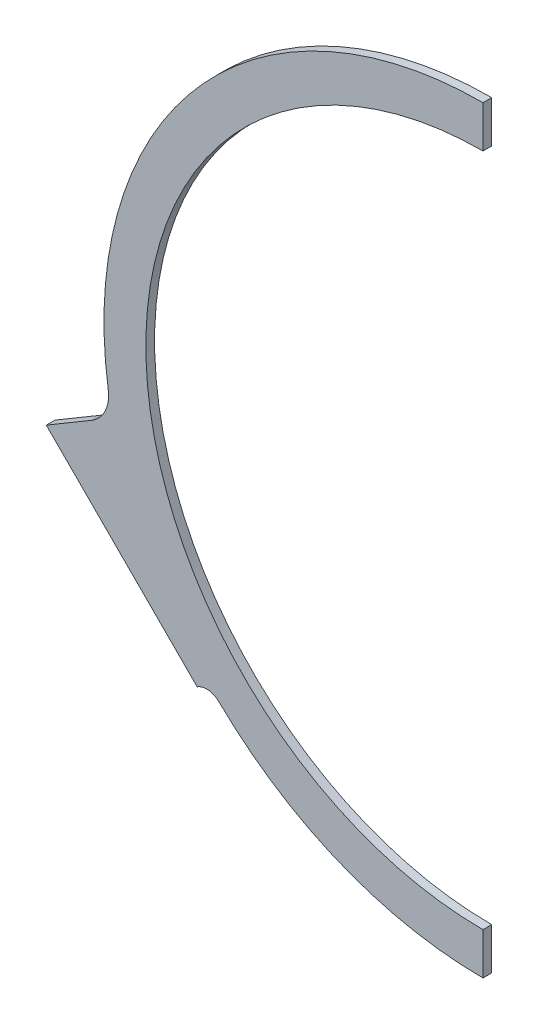
SolidWorks part; units mm, degrees
material "Balsa"
ref_plane "Front Plane" through (0, 0, 0) normal (0, 0, 1) x (1, 0, 0)
ref_plane "Top Plane" through (0, 0, 0) normal (0, 1, 0) x (1, 0, 0)
ref_plane "Right Plane" through (0, 0, 0) normal (1, 0, 0) x (0, 0, -1)
sketch "Sketch1" plane through (0, 0, 0) normal (0, 0, 1) x (1, 0, 0)
  line L0 (0, 0) -> (0, 499.9473) construction
  line L1 (0, -114.7984) -> (0, -129.4545) construction
  line L2 (0, -374.4718) -> (0, 404.2655) construction
  line L3 (-1.651, 142.9921) -> (-1.651, 150.6121) construction
  line L4 (1.651, 142.9921) -> (1.651, 150.6121) construction
  line L5 (-1.651, 142.9921) -> (1.651, 142.9921) construction
  line L6 (136.2041, -53.806) -> (0.0002, 24.7625) construction
  line L7 (-136.2076, -53.7991) -> (0.0002, 24.7625) construction
  line L8 (136.2041, -53.806) -> (0.0002, 24.7625) construction
  line L9 (-136.2076, -53.7991) -> (0.0002, 24.7625) construction
  line L10 (-125.0584, -45.4626) -> (-118.4576, -41.6554) construction
  line L11 (-123.6259, -48.4483) -> (-116.8078, -44.5157) construction
  line L12 (-118.4576, -41.6554) -> (-116.8078, -44.5157) construction
  line L13 (-124.1455, -48.7479) -> (-123.6847, -48.4822) construction
  line L14 (-123.6847, -48.4822) -> (-123.6259, -48.4483) construction
  line L15 (-125.7952, -45.8876) -> (-125.1113, -45.4931) construction
  line L16 (-125.1113, -45.4931) -> (-125.0584, -45.4626) construction
  line L17 (125.4797, -45.7137) -> (125.1075, -45.499) construction
  line L18 (123.8298, -48.5739) -> (123.6807, -48.488) construction
  line L19 (117.0223, -44.647) -> (118.6722, -41.7868) construction
  line L20 (123.6807, -48.488) -> (123.6228, -48.4545) construction
  line L21 (123.6228, -48.4545) -> (117.0223, -44.647) construction
  line L22 (125.1075, -45.499) -> (125.0554, -45.4689) construction
  line L23 (125.0554, -45.4689) -> (118.6722, -41.7868) construction
  line L24 (-107.079, -46.8884) -> (-120.3798, -54.5735)
  line L25 (-108.6638, -44.1348) -> (-121.9647, -51.8199)
  line L28 (-115.4206, -47.9666) -> (-121.9445, -51.7361) construction
  line L29 (-120.2754, -54.5131) -> (-108.646, -44.1245) construction
  line L30 (-114.4607, -49.3188) -> (-122.1124, -53.7399) construction
  line L31 (-113.7686, -50.8257) -> (-120.3665, -54.6379) construction
  line L32 (-115.4206, -47.9666) -> (-113.7686, -50.8257) construction
  line L33 (106.3137, -46.4532) -> (129.9098, -60.0883)
  line L34 (107.9004, -43.7007) -> (131.505, -57.3407)
  line L35 (129.9098, -60.0883) -> (131.505, -57.3407)
  line L36 (129.9098, -60.0883) -> (131.505, -57.3407) construction
  line L37 (107.9004, -43.7007) -> (131.505, -57.3407) construction
  line L38 (106.3137, -46.4532) -> (129.9098, -60.0883) construction
  line L39 (129.9098, -60.0883) -> (107.9004, -43.7007) construction
  line L40 (118.9051, -51.8945) -> (101.8722, -42.0519) construction
  line L41 (120.3631, -54.6438) -> (113.7655, -50.8313)
  line L42 (122.0152, -51.7848) -> (122.0057, -51.7794) construction
  line L43 (113.7655, -50.8313) -> (115.4176, -47.9723)
  line L44 (122.0057, -51.7794) -> (121.9413, -51.7421) construction
  line L45 (121.9413, -51.7421) -> (115.4176, -47.9723)
  line L46 (-108.6638, -44.1348) -> (-121.9647, -51.8199)
  line L47 (-107.079, -46.8884) -> (-120.3798, -54.5735)
  arc A0 (-1.651, 150.6121) -> (-125.0584, -45.4626) centre (0, 12.7) ccw
  circle A1 centre (0, 12.7) radius 120.904
  arc A2 (0, 150.622) -> (-1.651, 150.6121) centre (0, 12.7) ccw
  circle A3 centre (0, 12.7) radius 137.922 construction
  arc A4 (1.651, 150.6121) -> (0, 150.622) centre (0, 12.7) ccw
  arc A5 (-124.3508, -46.9604) -> (-123.6259, -48.4483) centre (0, 12.7) ccw
  arc A6 (-123.6259, -48.4483) -> (-121.9445, -51.7361) centre (0, 12.7) ccw
  arc A7 (-125.0584, -45.4626) -> (-124.3508, -46.9604) centre (0, 12.7) ccw
  arc A8 (124.3477, -46.9667) -> (125.0554, -45.4689) centre (0, 12.7) ccw
  arc A9 (125.0554, -45.4689) -> (1.651, 150.6121) centre (0, 12.7) ccw
  arc A10 (123.6228, -48.4545) -> (124.3477, -46.9667) centre (0, 12.7) ccw
  arc A11 (-121.9153, -51.7914) -> (-121.1641, -53.1919) centre (0, 12.7) ccw
  arc A12 (-120.3665, -54.6379) -> (120.3631, -54.6438) centre (0, 12.7) ccw
  arc A13 (-121.9445, -51.7361) -> (-121.9153, -51.7914) centre (0, 12.7) ccw
  arc A14 (-121.1641, -53.1919) -> (-120.3827, -54.6089) centre (0, 12.7) ccw
  arc A15 (-120.3827, -54.6089) -> (-120.397, -54.5834) centre (0, 12.7) ccw construction
  arc A16 (-120.397, -54.5834) -> (-120.3665, -54.6379) centre (0, 12.7) ccw construction
  arc A17 (120.3936, -54.5893) -> (121.0149, -53.4654) centre (0, 12.7) ccw construction
  arc A18 (121.9413, -51.7421) -> (123.6228, -48.4545) centre (0, 12.7) ccw
  arc A19 (120.3631, -54.6438) -> (120.3936, -54.5893) centre (0, 12.7) ccw construction
  arc A20 (121.0149, -53.4654) -> (121.9121, -51.7974) centre (0, 12.7) ccw construction
  arc A21 (121.9121, -51.7974) -> (121.9413, -51.7421) centre (0, 12.7) ccw construction
  spline S0 degree 3 poles (106.3137, -46.4532) (106.8426, -45.5357) (107.3715, -44.6182) (107.9004, -43.7007) knots 0 0 0 0 1 1 1 1 weights 1 1 1 1
  spline S1 degree 3 poles (-66.0123, 133.6164) (-70.0128, 131.4329) (-73.8716, 129.0699) (-81.3156, 123.9975) (-84.9009, 121.288) (-91.7995, 115.5249) (-95.113, 112.4712) (-99.0811, 108.4341) (-99.866, 107.6157) (-101.4182, 105.9565) (-102.1865, 105.1147) (-104.4569, 102.5643) (-105.9223, 100.8334) (-110.1768, 95.5512) (-115.4725, 88.2691) (-120.0285, 80.5179) (-123.1654, 74.5269) (-124.1643, 72.5002) (-125.5914, 69.415) (-126.0551, 68.3791) (-126.9587, 66.292) (-127.3989, 65.2397) (-129.5278, 59.9684) (-131.0098, 55.7) (-133.5456, 47.0638) (-134.5993, 42.696) (-136.2795, 33.8613) (-136.906, 29.3944) (-137.415, 23.7472) (-137.5031, 22.6146) (-137.6514, 20.3429) (-137.7116, 19.2049) (-137.8496, 15.7999) (-137.8852, 13.5361) (-137.8263, 6.7629) (-137.3062, -2.2197) (-135.9163, -11.1068) (-134.5433, -17.7359) (-134.0304, -19.9395) (-132.8922, -24.3345) (-132.2653, -26.5303) (-130.2347, -33.03) (-128.6774, -37.2656) (-126.1245, -43.2881) (-125.286, -45.1501) (-124.4066, -46.9926) knots 0 0 0 0 0.03125 0.03125 0.0625 0.0625 0.09375 0.09375 0.101563 0.101563 0.109375 0.109375 0.125 0.125 0.15625 0.1875 0.1875 0.203125 0.203125 0.210938 0.210938 0.21875 0.21875 0.25 0.25 0.28125 0.28125 0.3125 0.3125 0.320313 0.320313 0.328125 0.328125 0.34375 0.34375 0.375 0.40625 0.40625 0.421875 0.421875 0.4375 0.4375 0.46875 0.46875 0.48295 0.48295 0.48295 0.48295 construction
  spline S2 degree 3 poles (-2953.7904, 2461.9899) (-820.777, 189.8449) (-138.9507, -249.535) (81.4542, -98.9353) (85.033, -96.2237) (91.9188, -90.4573) (95.2258, -87.4025) (99.1858, -83.3647) (99.9691, -82.5461) (101.5182, -80.8868) (102.2849, -80.0449) (104.5506, -77.4941) (106.013, -75.7632) (110.2586, -70.4809) (112.9006, -66.8403) (117.8152, -59.3254) (120.0877, -55.4512) (123.2166, -49.4629) (124.2129, -47.4373) (125.6361, -44.3538) (126.0986, -43.3185) (126.9997, -41.2327) (127.4386, -40.181) (129.5618, -34.9121) (131.0396, -30.646) (133.5674, -22.0152) (134.6173, -17.6505) (136.2906, -8.8227) (136.914, -4.3596) (137.4197, 1.2823) (137.5071, 2.4139) (137.6542, 4.6834) (137.7138, 5.8206) (137.85, 9.2232) (137.8846, 11.4853) (137.8228, 18.2533) (137.2995, 27.2283) (135.9081, 36.1069) (134.5347, 42.7292) (134.0218, 44.9305) (132.8839, 49.3207) (132.2571, 51.5145) (130.2267, 58.0093) (128.67, 62.2416) (125.1615, 70.5162) (123.2097, 74.5586) (118.9108, 82.4534) (116.5637, 86.3058) (113.3753, 90.999) (112.7241, 91.9325) (111.3996, 93.7822) (110.7272, 94.697) (108.6802, 97.4113) (107.2757, 99.181) (102.9447, 104.3725) (96.8571, 110.9816) (90.1513, 116.9722) (84.8861, 121.2292) (83.0917, 122.6088) (80.3399, 124.6181) (79.4113, 125.2786) (77.543, 126.5731) (76.6028, 127.2075) (71.8708, 130.3161) (67.9881, 132.6004) (60.0328, 136.7739) (55.9603, 138.6631) (47.6249, 142.0446) (43.3619, 143.537) (37.9102, 145.1462) (36.8136, 145.4551) (34.6205, 146.0438) (33.5224, 146.3241) (30.2234, 147.1229) (28.0179, 147.5997) (21.3832, 148.8649) (16.9358, 149.4889) (7.993, 150.3014) (3.4975, 150.4899) (-3.2824, 150.4396) (-5.5486, 150.3672) (-10.0934, 150.1088) (-12.3559, 149.9236) (-19.101, 149.2046) (-23.5473, 148.5072) (-32.3412, 146.6856) (-36.6887, 145.5614) (-43.1354, 143.5526) (-45.2718, 142.8291) (-49.5193, 141.273) (-51.6323, 140.4395) (-369.2659, 5.9249) (-132.0865, -1278.1783) (677.8124, -3754.3927) knots -1.791229 -1.791229 -1.791229 -1.791229 0.03125 0.03125 0.0625 0.0625 0.09375 0.09375 0.101563 0.101563 0.109375 0.109375 0.125 0.125 0.15625 0.15625 0.1875 0.1875 0.203125 0.203125 0.210938 0.210938 0.21875 0.21875 0.25 0.25 0.28125 0.28125 0.3125 0.3125 0.320313 0.320313 0.328125 0.328125 0.34375 0.34375 0.375 0.40625 0.40625 0.421875 0.421875 0.4375 0.4375 0.46875 0.46875 0.5 0.5 0.53125 0.53125 0.539062 0.539062 0.546875 0.546875 0.5625 0.5625 0.59375 0.625 0.625 0.640625 0.640625 0.648437 0.648437 0.65625 0.65625 0.6875 0.6875 0.71875 0.71875 0.75 0.75 0.757812 0.757812 0.765625 0.765625 0.78125 0.78125 0.8125 0.8125 0.84375 0.84375 0.859375 0.859375 0.875 0.875 0.90625 0.90625 0.9375 0.9375 0.953125 0.953125 0.96875 0.96875 3.320852 3.320852 3.320852 3.320852 only from (66.1767, -108.566) to (-66.0123, 133.6164)
  spline S3 degree 3 poles (66.1767, -108.566) (70.1708, -106.3789) (74.0231, -104.0129) (81.4542, -98.9353) (85.033, -96.2237) (91.9188, -90.4573) (95.2258, -87.4025) (99.1858, -83.3647) (99.9691, -82.5461) (101.5182, -80.8868) (102.2849, -80.0449) (104.5506, -77.4941) (106.013, -75.7632) (110.2586, -70.4809) (112.9006, -66.8403) (117.8152, -59.3254) (120.0877, -55.4512) (123.2166, -49.4629) (124.2129, -47.4373) (125.6361, -44.3538) (126.0986, -43.3185) (126.9997, -41.2327) (127.4386, -40.181) (129.5618, -34.9121) (131.0396, -30.646) (133.5674, -22.0152) (134.6173, -17.6505) (136.2906, -8.8227) (136.914, -4.3596) (137.4197, 1.2823) (137.5071, 2.4139) (137.6542, 4.6834) (137.7138, 5.8206) (137.85, 9.2232) (137.8846, 11.4853) (137.8228, 18.2533) (137.2995, 27.2283) (135.9081, 36.1069) (134.5347, 42.7292) (134.0218, 44.9305) (132.8839, 49.3207) (132.2571, 51.5145) (130.2267, 58.0093) (128.67, 62.2416) (125.1615, 70.5162) (123.2097, 74.5586) (118.9108, 82.4534) (116.5637, 86.3058) (113.3753, 90.999) (112.7241, 91.9325) (111.3996, 93.7822) (110.7272, 94.697) (108.6802, 97.4113) (107.2757, 99.181) (102.9447, 104.3725) (96.8571, 110.9816) (90.1513, 116.9722) (84.8861, 121.2292) (83.0917, 122.6088) (80.3399, 124.6181) (79.4113, 125.2786) (77.543, 126.5731) (76.6028, 127.2075) (71.8708, 130.3161) (67.9881, 132.6004) (60.0328, 136.7739) (55.9603, 138.6631) (47.6249, 142.0446) (43.3619, 143.537) (37.9102, 145.1462) (36.8136, 145.4551) (34.6205, 146.0438) (33.5224, 146.3241) (30.2234, 147.1229) (28.0179, 147.5997) (21.3832, 148.8649) (16.9358, 149.4889) (7.993, 150.3014) (3.4975, 150.4899) (-3.2824, 150.4396) (-5.5486, 150.3672) (-10.0934, 150.1088) (-12.3559, 149.9236) (-19.101, 149.2046) (-23.5473, 148.5072) (-32.3412, 146.6856) (-36.6887, 145.5614) (-43.1354, 143.5526) (-45.2718, 142.8291) (-49.5193, 141.273) (-51.6323, 140.4395) (-57.9206, 137.7764) (-62.0153, 135.798) (-66.0123, 133.6164) knots 0 0 0 0 0.03125 0.03125 0.0625 0.0625 0.09375 0.09375 0.101563 0.101563 0.109375 0.109375 0.125 0.125 0.15625 0.15625 0.1875 0.1875 0.203125 0.203125 0.210938 0.210938 0.21875 0.21875 0.25 0.25 0.28125 0.28125 0.3125 0.3125 0.320313 0.320313 0.328125 0.328125 0.34375 0.34375 0.375 0.40625 0.40625 0.421875 0.421875 0.4375 0.4375 0.46875 0.46875 0.5 0.5 0.53125 0.53125 0.539062 0.539062 0.546875 0.546875 0.5625 0.5625 0.59375 0.625 0.625 0.640625 0.640625 0.648437 0.648437 0.65625 0.65625 0.6875 0.6875 0.71875 0.71875 0.75 0.75 0.757812 0.757812 0.765625 0.765625 0.78125 0.78125 0.8125 0.8125 0.84375 0.84375 0.859375 0.859375 0.875 0.875 0.90625 0.90625 0.9375 0.9375 0.953125 0.953125 0.96875 0.96875 1 1 1 1 construction
  spline S4 degree 3 poles (-124.4066, -46.9926) (-124.169, -47.4906) (-123.9283, -47.9871) (-123.6847, -48.4822) knots 0.48295 0.48295 0.48295 0.48295 0.486788 0.486788 0.486788 0.486788 construction
  spline S5 degree 3 poles (-123.6847, -48.4822) (-122.846, -50.1865) (-121.9718, -51.874) (-118.9108, -57.4955) (-116.5612, -61.3517) (-113.369, -66.0497) (-112.7169, -66.9844) (-111.3913, -68.8351) (-110.7184, -69.7503) (-108.6697, -72.4662) (-107.264, -74.2369) (-102.929, -79.4315) (-96.8353, -86.0447) (-90.1214, -92.0392) (-84.8493, -96.299) (-83.0524, -97.6795) (-80.2967, -99.6899) (-79.367, -100.3507) (-77.4971, -101.6451) (-76.5559, -102.2795) (-71.8198, -105.3881) (-67.9332, -107.6723) (-59.9695, -111.8452) (-55.8924, -113.7339) (-47.5468, -117.114) (-43.2782, -118.6053) (-37.8188, -120.2127) (-36.7216, -120.521) (-34.5268, -121.1085) (-33.4279, -121.3881) (-30.1264, -122.185) (-27.9191, -122.6605) (-21.2788, -123.9216) (-16.8274, -124.5426) (-7.8757, -125.3484) (-3.3755, -125.5332) (3.4122, -125.4766) (5.6812, -125.4019) (10.231, -125.1387) (12.493, -124.9512) (19.2413, -124.2249) (23.6899, -123.5224) (32.4889, -121.6898) (36.8393, -120.5597) (43.2904, -118.5412) (45.4283, -117.8143) (48.6163, -116.6419) (49.6759, -116.2374) (51.7885, -115.4006) (52.8426, -114.968) (58.0839, -112.7404) (62.1792, -110.755) (66.1767, -108.566) knots 0.486788 0.486788 0.486788 0.486788 0.5 0.5 0.53125 0.53125 0.539062 0.539062 0.546875 0.546875 0.5625 0.5625 0.59375 0.625 0.625 0.640625 0.640625 0.648437 0.648437 0.65625 0.65625 0.6875 0.6875 0.71875 0.71875 0.75 0.75 0.757812 0.757812 0.765625 0.765625 0.78125 0.78125 0.8125 0.8125 0.84375 0.84375 0.859375 0.859375 0.875 0.875 0.90625 0.90625 0.9375 0.9375 0.953125 0.953125 0.960937 0.960937 0.96875 0.96875 1 1 1 1 construction
  spline S6 degree 3 poles (-108.6638, -44.1348) (-108.1355, -45.0527) (-107.6073, -45.9705) (-107.079, -46.8884) knots 0 0 0 0 1 1 1 1 weights 1 1 1 1
  spline S7 degree 3 poles (-121.9647, -51.8199) (-121.4364, -52.7377) (-120.9081, -53.6556) (-120.3798, -54.5735) knots 0 0 0 0 1 1 1 1 weights 1 1 1 1
  spline S8 degree 3 poles (-1893.2904, -3504.9521) (-555.0999, -1197.2897) (777.7409, 1114.8667) (2098.5249, 3419.8483) knots -1257.71527 -1257.71527 -1257.71527 -1257.71527 1261.282288 1261.282288 1261.282288 1261.282288 weights 1.001261 0.999578 0.999579 1.001266 only from (106.3137, -46.4532) to (107.9004, -43.7007)
  spline S9 degree 3 poles (-121.8597, -51.7592) (-121.5948, -52.2177) (-121.3299, -52.6762) (-121.065, -53.1347) knots 0 0 0 0 0.5 0.5 0.5 0.5 weights 1 1 1 1 construction
  spline S12 degree 3 poles (-2107.5184, 3411.1282) (-794.411, 1112.1626) (537.2029, -1201.4874) (1876.5356, -3511.0638) knots -1261.624621 -1261.624621 -1261.624621 -1261.624621 1257.384167 1257.384167 1257.384167 1257.384167 weights 1.00204 0.999326 0.99932 1.002023 only from (-121.9647, -51.8199) to (-120.3798, -54.5735)
  spline S13 degree 3 poles (-2094.7969, 3419.3607) (-780.7303, 1119.4679) (550.7427, -1194.0569) (1889.8709, -3504.2883) knots -1261.518414 -1261.518414 -1261.518414 -1261.518414 1257.484402 1257.484402 1257.484402 1257.484402 weights 1.00184 0.999392 0.999387 1.001825 only from (-108.6638, -44.1348) to (-107.079, -46.8884)
  point P7 (0, -125.5003)
  point P8 (0, 150.4602)
  point P25 (-125.0584, -45.4626)
  point P38 (123.6228, -48.4545)
  dimension "D2" = 275.844
  dimension "D1" = 275.9605
  dimension "D3" = 12.7
  dimension "D5" = 3.302
  dimension "D6" = 7.62
  dimension "D7" = 3.302
  dimension "D8" = 7.62
  dimension "D9" = 3.302
  dimension "D10" = 7.62
  dimension "D11" = 3.302
  dimension "D12" = 7.62
  dimension "D13" = 3.302
  dimension "D14" = 7.62
  dimension "D4" = 17.018
extrude "Boss-Extrude1" [suppressed] add sketch "Sketch1" along normal mid plane 3.175
sketch "Sketch2" plane through (248.2736, -245.0135, 0) normal (0, 0, -1) x (0, -1, 0)
  line L3 (-245.0135, 248.2736) -> (-427.6569, 248.2736) construction
  circle A1 centre (-257.7135, 248.2736) radius 137.922
  circle A16 centre (-257.7135, 248.2736) radius 122.682
  dimension "D1" = 12.7
  dimension "D2" = 275.844
  dimension "D3" = 15.24
fillet "Fillet1" [suppressed] radius 1.27
extrude "Boss-Extrude2" add sketch "Sketch2" along normal mid plane 3.175
sketch "Sketch3" plane through (0, 0, 0) normal (1, 0, 0) x (0, 0, -1)
  line L1 (-141.282, 263.3615) -> (149.6958, 263.3615)
  line L2 (-141.282, 263.3615) -> (-141.282, -241.4673)
  line L3 (-141.282, -241.4673) -> (149.6958, -241.4673)
  line L4 (149.6958, 263.3615) -> (149.6958, -241.4673)
extrude "Cut-Extrude1" cut sketch "Sketch3" along normal through all
sketch "Sketch4" plane through (0, 0, 0) normal (0, 0, 1) x (1, 0, 0)
  line L0 (0, 0) -> (-214.0513, 0) construction
  line L1 (-158.912, -30.4526) -> (-104.0071, -85.469)
  line L2 (-134.8591, -16.205) -> (-158.912, -30.4526)
  arc A0 (-104.0071, -85.469) -> (-167.1792, -137.0342) centre (409.8935, -779.5232) ccw construction
  arc A1 (0, 150.622) -> (0, -125.222) centre (0, 12.7) ccw construction
  arc A2 (-99.8692, -82.4242) -> (-104.0071, -85.469) centre (409.8935, -779.5232) ccw
  arc A3 (-134.8591, -16.205) -> (-99.8692, -82.4242) centre (0, 12.7) ccw
  point P6 (-99.8692, -82.4242)
  dimension "D3" = 54.61
  dimension "D5" = 863.6
  dimension "D1" = 99.8692
  dimension "D2" = 82.4242
  dimension "D4" = 67.31
  dimension "D6" = 45.058
  dimension "D7" = 133.9931
  dimension "D8" = 134.8591
  dimension "D9" = 30.64
extrude "Boss-Extrude3" add sketch "Sketch4" along normal mid plane 3.175
fillet "Fillet2" radius 6.35 1 edges at (-99.8692, -82.4242, 0)
fillet "Fillet3" radius 12.7 1 edges at (-134.8591, -16.205, 0)
equation "\"slotwidth\"=0.13"
equation "\"D11@Sketch1\"=\"slotwidth\""
